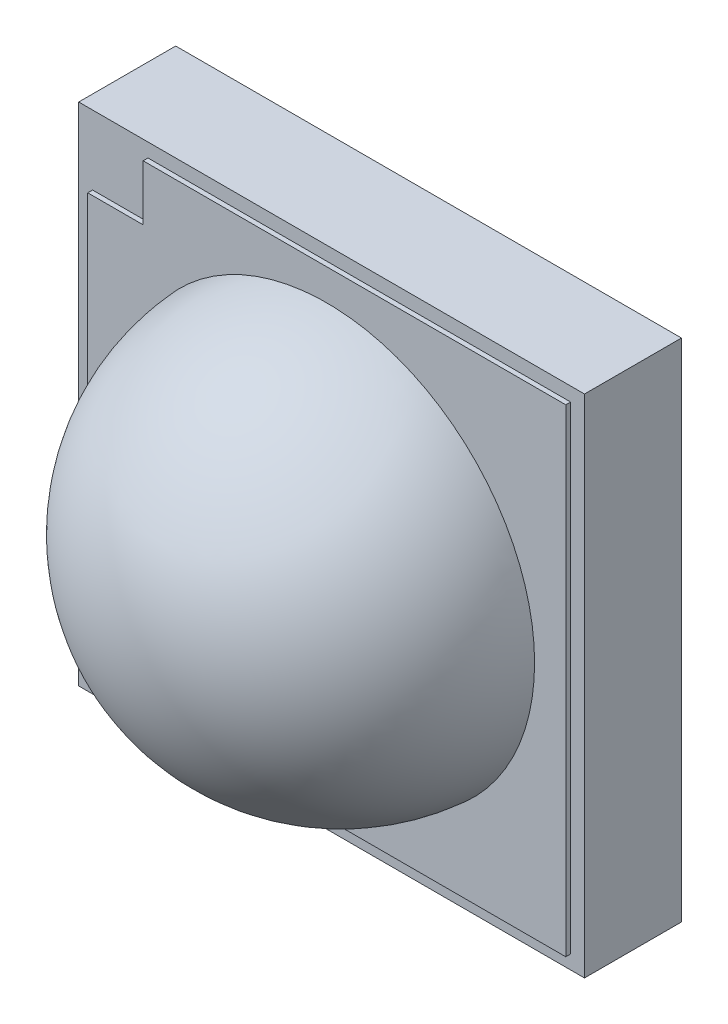
SolidWorks part; units mm, degrees
ref_plane "Front" through (0, 0, 0) normal (0, 0, 1) x (1, 0, 0)
ref_plane "Top" through (0, 0, 0) normal (0, 1, 0) x (1, 0, 0)
ref_plane "Right" through (0, 0, 0) normal (1, 0, 0) x (0, 0, -1)
sketch "Эскиз1" plane through (0, 0, 0) normal (0, 0, 1) x (1, 0, 0)
  line L1 (0.725, -1.625) -> (-0.525, -1.625)
  line L2 (0.725, -1.625) -> (0.725, 1.625)
  line L3 (0.725, 1.625) -> (-0.725, 1.625)
  line L4 (-0.725, -1.425) -> (-0.725, 1.625)
  line L5 (0.725, -1.625) -> (-0.725, 1.625) construction
  line L6 (0.725, 1.625) -> (-0.725, -1.625) construction
  line L7 (1.635, -1.625) -> (1.105, -1.625)
  line L8 (-1.105, -1.625) -> (-1.635, -1.625)
  line L9 (-1.105, -1.625) -> (-1.105, -0.875)
  line L10 (-1.105, -0.875) -> (-1.635, -0.875)
  line L11 (-1.635, -1.625) -> (-1.635, -0.875)
  line L12 (-1.105, -1.625) -> (-1.635, -0.875) construction
  line L13 (-1.105, -0.875) -> (-1.635, -1.625) construction
  line L14 (1.635, -1.625) -> (1.635, -0.875)
  line L15 (1.635, -0.875) -> (1.105, -0.875)
  line L16 (1.105, -1.625) -> (1.105, -0.875)
  line L17 (1.635, -0.375) -> (1.105, -0.375)
  line L18 (1.635, -0.375) -> (1.635, 0.375)
  line L19 (1.635, 0.375) -> (1.105, 0.375)
  line L20 (1.105, -0.375) -> (1.105, 0.375)
  line L21 (1.635, 0.875) -> (1.105, 0.875)
  line L22 (1.635, 0.875) -> (1.635, 1.625)
  line L23 (1.635, 1.625) -> (1.105, 1.625)
  line L24 (1.105, 0.875) -> (1.105, 1.625)
  line L25 (-1.105, -0.375) -> (-1.635, -0.375)
  line L26 (-1.105, -0.375) -> (-1.105, 0.375)
  line L27 (-1.105, 0.375) -> (-1.635, 0.375)
  line L28 (-1.635, -0.375) -> (-1.635, 0.375)
  line L29 (-1.105, 0.875) -> (-1.635, 0.875)
  line L30 (-1.105, 0.875) -> (-1.105, 1.625)
  line L31 (-1.105, 1.625) -> (-1.635, 1.625)
  line L32 (-1.635, 0.875) -> (-1.635, 1.625)
  line L34 (-0.525, -1.625) -> (-0.725, -1.425)
  point P0 (0, 0)
  point P3 (0, 0)
  point P5 (-0.7228, 1.63)
  point P8 (-1.37, -1.25)
  point P14 (-0.7184, 1.6103)
  point P15 (0, 0)
  point P38 (0, 0)
  dimension "D1" = 1.45
  dimension "D2" = 3.25
  dimension "D4" = 0.53
  dimension "D5" = 0.75
  dimension "D6" = 0.38
  dimension "D9" = 3.27
  dimension "D10" = 0.5
  dimension "D7" = 2
  dimension "D8" = 3
extrude "Бобышка-Вытянуть1" add sketch "Эскиз1" along normal blind 0.035
sketch "Эскиз2" plane through (0, 0, 0.035) normal (0, 0, 1) x (1, 0, 0)
  line L1 (-1.825, -1.825) -> (1.825, -1.825)
  line L2 (-1.825, -1.825) -> (-1.825, 1.825)
  line L3 (-1.825, 1.825) -> (1.825, 1.825)
  line L4 (1.825, -1.825) -> (1.825, 1.825)
  line L5 (-1.825, -1.825) -> (1.825, 1.825) construction
  line L6 (-1.825, 1.825) -> (1.825, -1.825) construction
  point P0 (0, 0)
  dimension "D1" = 3.65
extrude "Бобышка-Вытянуть2" add sketch "Эскиз2" along normal blind 0.7
sketch "Эскиз4" plane through (0, 0, 0.735) normal (0, 0, 1) x (1, 0, 0)
  line L0 (1.725, 1.725) -> (1.725, -1.725)
  line L5 (-1.725, -1.725) -> (1.725, 1.725) construction
  line L6 (-1.725, 1.725) -> (1.725, -1.725) construction
  line L9 (1.725, -1.725) -> (-1.725, -1.725)
  line L10 (1.725, 1.725) -> (-1.325, 1.725)
  line L11 (-1.325, 1.725) -> (-1.325, 1.325)
  line L12 (-1.325, 1.325) -> (-1.725, 1.325)
  line L13 (-1.725, 1.325) -> (-1.725, -1.725)
  line L14 (-1.725, 1.325) -> (-1.725, 1.725) construction
  line L15 (-1.725, 1.725) -> (-1.325, 1.725) construction
  point P0 (0, 0)
  dimension "D1" = 3.45
  dimension "D2" = 0.4
extrude "Бобышка-Вытянуть3" add sketch "Эскиз4" along normal blind 0.035
sketch "Эскиз3" plane through (0, 0, 0) normal (0, 1, 0) x (1, 0, 0)
  line L0 (0, -0.77) -> (0, -2.17)
  line L1 (0, -0.77) -> (-1.5, -0.77)
  line L3 (1.725, -0.77) -> (-1.325, -0.77) construction
  arc A0 (-1.5, -0.77) -> (0, -2.17) centre (0, -0.6664) ccw
  point P6 (-0.0967, -0.77)
  point P8 (0, 0)
  point P9 (0, 0)
  dimension "D1" = 1.4
  dimension "D2" = 1.5
revolve "Повернуть1" add sketch "Эскиз3" angle 360 about L0
